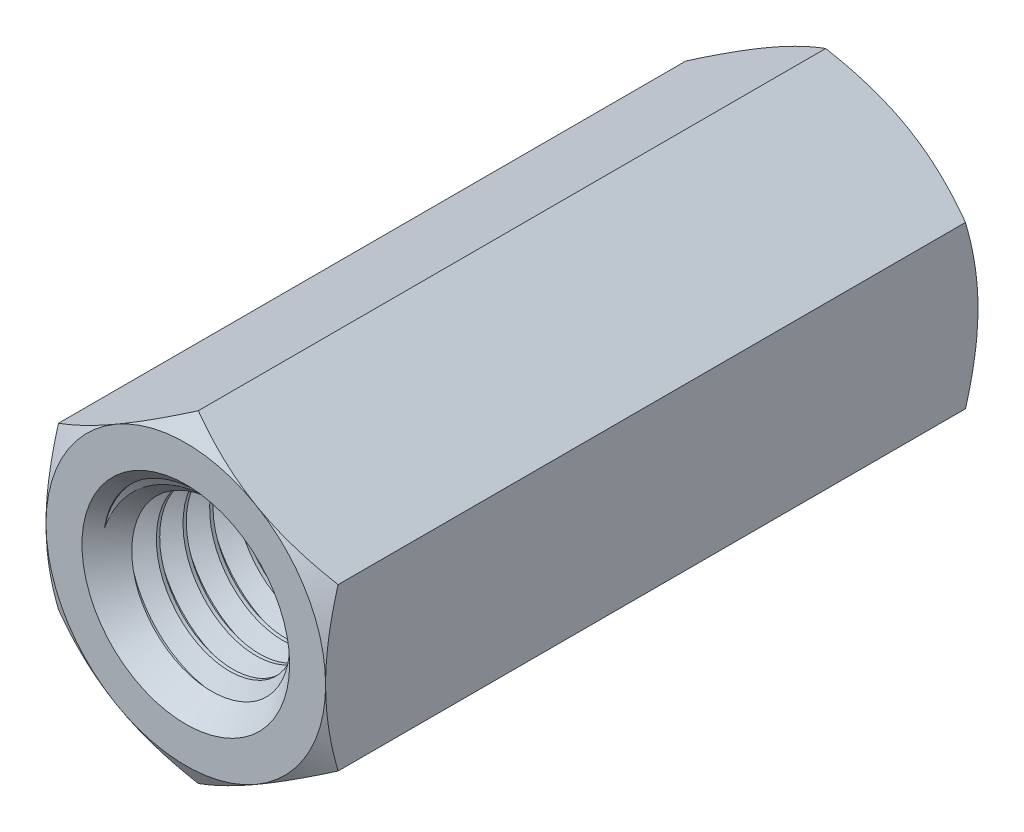
SolidWorks part; units mm, degrees
material "AISI 304"
ref_plane "Front Plane" through (0, 0, 0) normal (0, 0, 1) x (1, 0, 0)
ref_plane "Top Plane" through (0, 0, 0) normal (0, 1, 0) x (1, 0, 0)
ref_plane "Right Plane" through (0, 0, 0) normal (1, 0, 0) x (0, 0, -1)
sketch "Sketch1" plane through (0, 0, 0) normal (0, 0, 1) x (1, 0, 0)
  line L1 (0, 5.4993) -> (-4.7625, 2.7496)
  line L2 (-4.7625, 2.7496) -> (-4.7625, -2.7496)
  line L3 (-4.7625, -2.7496) -> (0, -5.4993)
  line L4 (0, -5.4993) -> (4.7625, -2.7496)
  line L5 (4.7625, -2.7496) -> (4.7625, 2.7496)
  line L6 (4.7625, 2.7496) -> (0, 5.4993)
  circle A0 centre (0, 0) radius 4.7625 construction
  dimension "Hex" = 9.525
extrude "Extrude1" add sketch "Sketch1" against normal blind 22.225
sketch "Sketch2" plane through (0, 0, 0) normal (0, 0, 1) x (1, 0, 0)
  circle A0 centre (0, 0) radius 4.7625 construction
  circle A1 centre (0, 0) radius 4.7625
extrude "Cut-Extrude1" cut sketch "Sketch2" against normal through all draft 60 flip side to cut
sketch "Sketch3" plane through (0, 0, -22.225) normal (0, 0, -1) x (-1, 0, 0)
  circle A1 centre (0, 0) radius 4.7625
  circle A2 centre (0, 0) radius 4.7625
  dimension "D1" = 0
extrude "Cut-Extrude2" cut sketch "Sketch3" against normal through all draft 60 flip side to cut
sketch "Sketch4" plane through (0, 0, 0) normal (0, 0, 1) x (1, 0, 0)
  circle A0 centre (0, 0) radius 3.175
  dimension "Thread Dia" = 6.35
extrude "Cut-Extrude3" cut sketch "Sketch4" against normal through all
sketch "Sketch7" plane through (0, 0, 0) normal (0, 0, 1) x (1, 0, 0)
  circle A4 centre (0, 0) radius 3.5379
  circle A5 centre (0, 0) radius 3.5379
  dimension "D1" = 0.3629
sketch "Sketch8" plane through (0, 0, -22.225) normal (0, 0, -1) x (-1, 0, 0)
  circle A1 centre (0, 0) radius 3.5379
  circle A2 centre (0, 0) radius 3.5379 construction
sketch "Sketch5" plane through (0, 0, 0) normal (0, 0, 1) x (1, 0, 0)
  circle A0 centre (0, 0) radius 3.175 construction
  circle A1 centre (0, 0) radius 3.175
curve "Helix/Spiral1" pitch 0.9071 height 23.1321 turns 25.5 parameters "pitch"=0.9071
sketch "Sketch9" plane through (0, 0, 0) normal (1, 0, 0) x (0, 0, -1)
  line L0 (-0.4536, 3.175) -> (-0.3402, 3.175)
  line L1 (-0.3402, 3.175) -> (0, 2.5858)
  line L2 (-0.4536, 3.175) -> (-0.7937, 2.5858)
  line L3 (-0.7937, 2.5858) -> (0, 2.5858)
  line L4 (-0.3969, 3.175) -> (-0.3969, 2.5858) construction
  line L5 (-0.6237, 2.8804) -> (-0.1701, 2.8804) construction
  line L7 (0, 2.5858) -> (0, 3.175) construction
  line L8 (0, 3.175) -> (0, -3.175) construction
  dimension "D1" = 0.1134
  dimension "D2" = 0.4536
  dimension "D3" = 60
sketch "Sketch12" plane through (0, 0, 0) normal (0, 0, 1) x (1, 0, 0)
  circle A0 centre (0, 0) radius 2.5858
  circle A1 centre (0, 0) radius 3.175 construction
  circle A2 centre (0, 0) radius 3.175
extrude "Extrude2" add sketch "Sketch12" against normal up to surface (22.225 mm away) up to face at (3.175, 0, -22.225)
sweep "Cut-Sweep1" cut profiles "Sketch9" path "Helix/Spiral1"
extrude "Cut-Extrude6" cut sketch "Sketch7" against normal through all draft 45
extrude "Cut-Extrude7" cut sketch "Sketch8" against normal through all draft 45
sketch "Sketch15" plane through (0, 0, 0) normal (0, -1, 0) x (1, 0, 0)
  circle A0 centre (-6.1625, -10.875) radius 4.7625 construction
  circle A1 centre (6.1625, -10.875) radius 4.7625 construction
  circle A2 centre (-6.1625, -10.875) radius 4.7625
  circle A3 centre (6.1625, -10.875) radius 4.7625
extrude "Cut-Extrude9" [suppressed] cut sketch "Sketch15" against normal through all and the other way through all
sketch "Sketch16" plane through (0, 0, 0) normal (0, -1, 0) x (1, 0, 0)
  circle A0 centre (0, -19.05) radius 0.5
  circle A1 centre (0, -19.05) radius 0.5 construction
extrude "Cut-Extrude10" [suppressed] cut sketch "Sketch16" along normal through all
equation "\"D1@Sketch7\" = \"pitch@Helix/Spiral1\"*.4"
equation "\"D2@Sketch9\" = \"pitch@Helix/Spiral1\"*.5"
equation "\"D3@Helix/Spiral1\" = \"pitch@Helix/Spiral1\"+\"Height@Extrude1\""
equation "\"D1@Sketch9\" = \"pitch@Helix/Spiral1\"*.125"
